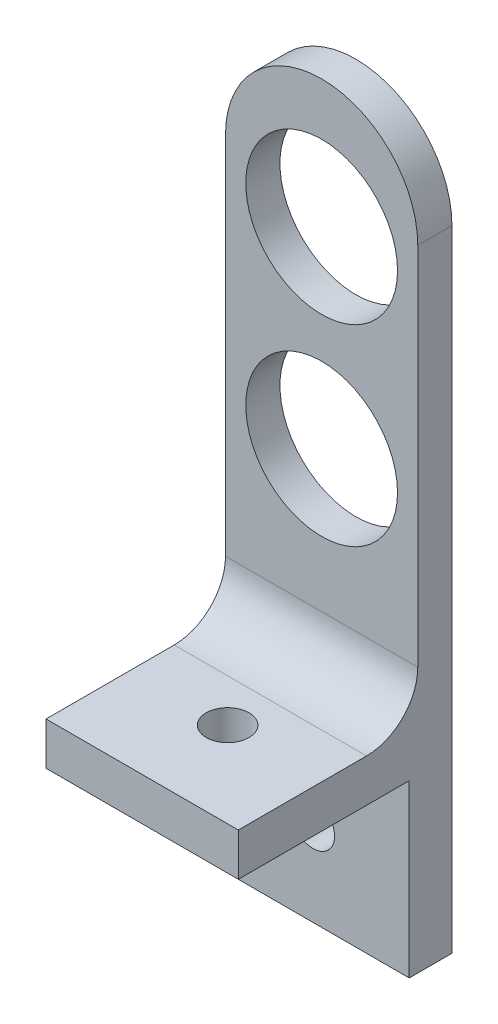
SolidWorks part; units mm, degrees
ref_plane "Front Plane" through (0, 0, 0) normal (0, 0, 1) x (1, 0, 0)
ref_plane "Top Plane" through (0, 0, 0) normal (0, 1, 0) x (1, 0, 0)
ref_plane "Right Plane" through (0, 0, 0) normal (1, 0, 0) x (0, 0, -1)
sketch "Sketch1" plane through (0, 0, 0) normal (0, 0, 1) x (1, 0, 0)
  line L1 (-14.2875, 53.975) -> (14.2875, 53.975)
  line L2 (-14.2875, 53.975) -> (-14.2875, -53.975)
  line L3 (-14.2875, -53.975) -> (14.2875, -53.975)
  line L4 (14.2875, 53.975) -> (14.2875, -53.975)
  line L5 (-14.2875, 53.975) -> (14.2875, -53.975) construction
  line L6 (-14.2875, -53.975) -> (14.2875, 53.975) construction
  line L7 (-14.2875, -28.575) -> (14.2875, -28.575)
  line L8 (-14.2875, -28.575) -> (-14.2875, -22.225)
  line L9 (-14.2875, -22.225) -> (14.2875, -22.225)
  line L10 (14.2875, -28.575) -> (14.2875, -22.225)
  line L11 (-14.2875, -28.575) -> (14.2875, -22.225) construction
  line L12 (-14.2875, -22.225) -> (14.2875, -28.575) construction
  circle A0 centre (0, 6.35) radius 11.2776
  circle A1 centre (0, 34.925) radius 11.2776
  circle A2 centre (0, -41.275) radius 3.1877
  point P0 (0, 0)
  point P12 (-4.3591, -26.9431)
  point P13 (0, -25.4)
  dimension "D6" = 22.5552
  dimension "D7" = 6.3754
  dimension "D1" = 28.575
  dimension "D2" = 107.95
  dimension "D3" = 12.7
  dimension "D4" = 60.325
  dimension "D5" = 88.9
  dimension "D8" = 25.4
  dimension "D9" = 6.35
extrude "Boss-Extrude1" add sketch "Sketch1" along normal blind 5.08 contours L2 L9 L4 L1 A1 A0 region at (0, 53.1612, 0)
extrude "Boss-Extrude2" add sketch "Sketch1<3>" along normal blind 6.35 separate body contours L7 L2 L3 L4 A2 region at (0, -28.9573, 0)
sketch "Sketch1<3>" plane through (0, 0, 0) normal (0, 0, 1) x (1, 0, 0) same geometry as "Sketch1"
extrude "Boss-Extrude3" add sketch "Sketch1<4>" along normal blind 31.75 contours L9 L2 L7 L4 region at (0, -25.4, 0)
sketch "Sketch1<4>" plane through (0, 0, 0) normal (0, 0, 1) x (1, 0, 0) same geometry as "Sketch1"
fillet "Fillet1" radius 7.62 1 edges at (0, -22.225, 5.08)
fillet "Fillet3" 2 edges at (-14.2875, 53.975, 2.54) (14.2875, 53.975, 2.54) type full round first side face at (-14.2875, -13.087, 10.8313) second side face at (14.2875, -13.087, 10.8313) middle face at (0, 53.975, 2.54)
sketch "Sketch2" plane through (0, -28.575, 0) normal (0, -1, 0) x (1, 0, 0)
  line L0 (-14.2875, 31.75) -> (-14.2875, 6.35) construction
  circle A0 centre (0, 19.05) radius 3.1877
  point P2 (-14.2875, 19.05)
  dimension "D1" = 6.3754
extrude "Cut-Extrude1" cut sketch "Sketch2" against normal through all
